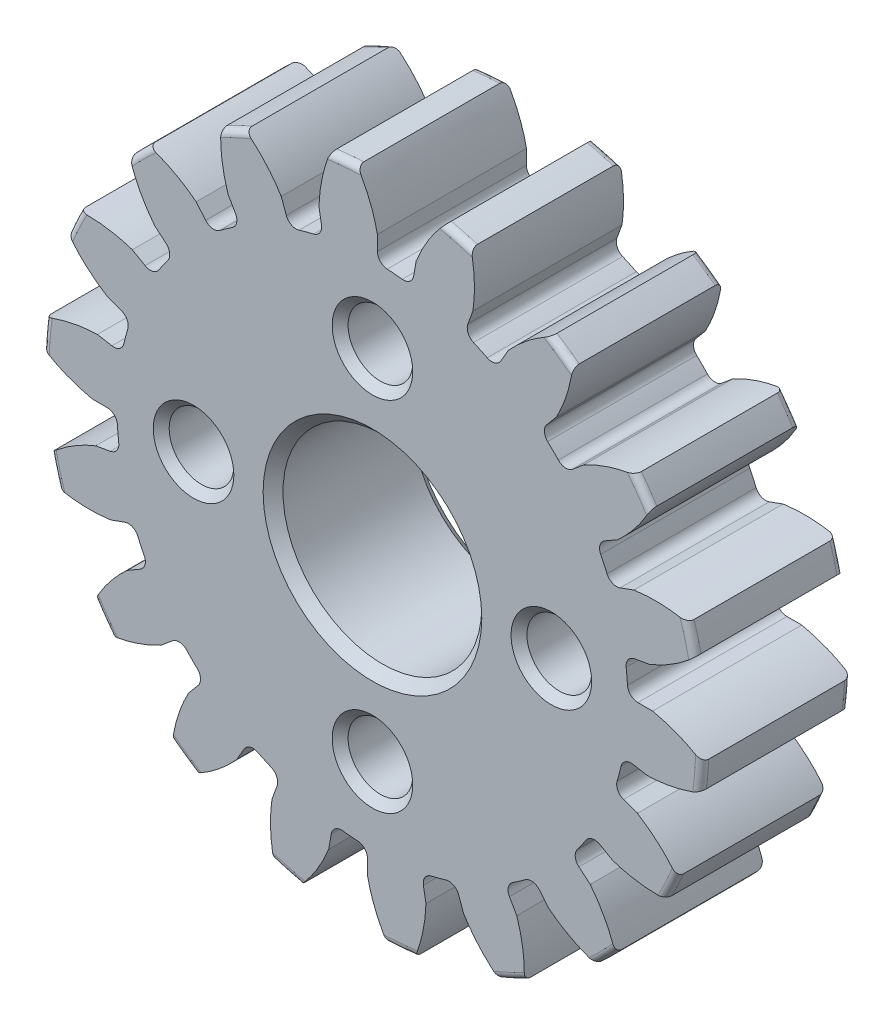
SolidWorks part; units mm, degrees
material "Plain Carbon Steel"
ref_plane "Front" through (0, 0, 0) normal (0, 0, 1) x (1, 0, 0)
ref_plane "Top" through (0, 0, 0) normal (0, 1, 0) x (1, 0, 0)
ref_plane "Right" through (0, 0, 0) normal (1, 0, 0) x (0, 0, -1)
sketch "Sketch1" plane through (0, 0, 0) normal (0, 0, 1) x (1, 0, 0)
  line L0 (-228.6, 0) -> (228.6, 0) construction
  circle A0 centre (0, 0) radius 10.541
  circle A1 centre (0, 0) radius 9.525 construction
  circle A3 centre (0, 0) radius 8.1598 construction
  dimension "D3" = 1.016
  dimension "D1" = 2.3813
extrude "Boss-Extrude1" add sketch "Sketch1" against normal blind 4.7625
sketch "Sketch2" plane through (0, 0, 0) normal (1, 0, 0) x (0, 0, -1)
  line L0 (4.7625, 0) -> (11.0998, 0)
  line L1 (4.7625, 0) -> (4.7625, 6.35)
  line L2 (4.7625, 6.35) -> (11.0998, 6.35)
  line L3 (11.0998, 6.35) -> (11.0998, 0)
  point P5 (11.0998, -6.35)
  point P6 (0, -10.541)
  point P7 (4.7625, -10.541)
  point P9 (0, 10.541)
revolve "Revolve1" add sketch "Sketch2" angle 360 mid plane about L0
fillet "Fillet2" radius 0.2108 3 edges at (10.541, 0, -4.7625) (10.541, 0, 0) (6.35, 0, -4.7625)
sketch "Sketch3" plane through (0, 0, 0) normal (0, 0, 1) x (1, 0, 0)
  line L0 (0, 0) -> (0, 10.541) construction
  line L1 (-3.0613, 8.4108) -> (0, 9.525)
  line L2 (-9.5921, 9.525) -> (9.5921, 9.525) construction
  line L3 (-9.0136, 6.2443) -> (9.0136, 12.8057) construction
  line L4 (-3.0613, 8.4108) -> (0, 0) construction
  line L5 (-7.3721, 5.0759) -> (0, 0) construction
  line L6 (-7.3721, 5.0759) -> (-2.3984, 12.2997) construction
  line L7 (-2.1265, 8.6943) -> (0, 0) construction
  line L8 (-2.1265, 8.6943) -> (0.0886, 9.2361) construction
  arc A0 (-3.0613, 8.4108) -> (-7.3721, 5.0759) centre (0, 0) ccw
  circle A1 centre (0, 0) radius 9.525 construction
  circle A2 centre (0, 0) radius 8.9506 construction
  arc A3 (-3.0613, 8.4108) -> (-2.1265, 8.6943) centre (0, 0) cw
  circle A4 centre (0, 0) radius 10.541 construction
  point P6 (0, 9.525)
  dimension "D1" = 3.2577
  dimension "Pressure Angle" = 20
  dimension "D2" = 5.5382
  dimension "D3" = 8.7705
  dimension "D4" = 0.9773
  dimension "D5" = 2.2804
sketch "Sketch4" plane through (0, 0, 0) normal (0, 0, 1) x (1, 0, 0)
  line L0 (0, 0) -> (0.827, 9.4526) construction
  line L1 (0.1576, 8.9492) -> (0.1576, 8.1582)
  line L2 (0, 9.525) -> (1.654, 9.3803) construction
  line L3 (1.3988, 8.8406) -> (1.2615, 8.0616)
  line L4 (0.1576, 8.1582) -> (0, 0) construction
  line L5 (0, 0) -> (0, 10.541) construction
  line L6 (-7.3721, 5.0759) -> (-2.3984, 12.2997) construction
  line L7 (-7.3721, 5.0759) -> (-2.3984, 12.2997) construction
  arc A0 (1.2615, 8.0616) -> (0.1576, 8.1582) centre (0, 0) ccw
  arc A1 (0, 9.525) -> (1.654, 9.3803) centre (0, 0) cw construction
  circle A2 centre (0, 0) radius 9.525 construction
  circle A3 centre (0, 0) radius 8.9506 construction
  circle A4 centre (0, 0) radius 8.1598 construction
  arc A5 (4.4978, 11.6964) -> (-2.3984, 12.2997) centre (0, 0) ccw
  spline S0 degree 2 poles (-2.3984, 12.2997) (-0.2792, 11.04) (0.1576, 8.9492) knots 0 0 0 1 1 1
  spline S1 degree 2 poles (4.4978, 11.6964) (2.1921, 10.8237) (1.3988, 8.8406) knots 0 0 0 1 1 1
  dimension "D1" = 1.6624
extrude "Cut-Extrude1" cut sketch "Sketch4" against normal through all
fillet "Fillet1" radius 0.3325 2 edges at (1.2615, 8.0616, -2.3813) (0.1576, 8.1582, -2.3813)
pattern_circular "CirPattern1" count 18 over 360 about axis through (0, 0, -4.7625) along (0, 0, 1) of "Cut-Extrude1", "Fillet1"
sketch "Sketch5" plane through (0, 0, 0) normal (0, 0, 1) x (1, 0, 0)
  line L0 (0, 4.3663) -> (0, 0) construction
  line L1 (-1.1906, 2.9433) -> (1.1906, 2.9433) construction
  line L2 (-1.1906, 2.9433) -> (-1.1906, 4.3663) construction
  line L3 (-1.1906, 4.3663) -> (1.1906, 4.3663) construction
  line L4 (1.1906, 2.9433) -> (1.1906, 4.3663) construction
  line L5 (-1.1906, 2.9433) -> (1.1906, 4.3663) construction
  line L6 (-1.1906, 4.3663) -> (1.1906, 2.9433) construction
  circle A0 centre (0, 0) radius 3.175
  point P3 (0, 3.6548)
  point P8 (0, 3.175)
  point P9 (0, -3.175)
  dimension "Bore Min" = 6.35
  dimension "Keyway Wd" = 2.3813
  dimension "Keyway Dpt." = 1.1913
extrude "Cut-Extrude2" cut sketch "Sketch5" against normal through all
sketch "Pitch Dia" plane through (0, 0, 0) normal (0, 0, 1) x (1, 0, 0)
  circle A0 centre (0, 0) radius 9.525 construction
  circle A1 centre (0, 0) radius 9.525 construction
sketch "Sketch6" plane through (0, 0, -4.7625) normal (0, 0, -1) x (-1, 0, 0)
  circle A0 centre (0, 0) radius 9.525
  dimension "D1" = 19.05
extrude "Cut-Extrude3" cut sketch "Sketch6" along normal through all
chamfer "Chamfer1" distance 0.3175 angle 45 2 edges at (3.175, 0, 0) (-3.175, 0, -4.7625)
sketch "Sketch7" plane through (0, 0, -4.7625) normal (0, 0, -1) x (-1, 0, 0)
  line L0 (0, 10.28) -> (0, -11.7668) construction
  line L1 (-13.3938, 0) -> (13.601, 0) construction
  circle A4 centre (0, 0) radius 5.715 construction
  circle A5 centre (0, 5.715) radius 1.0325
  circle A6 centre (-5.715, 0) radius 1.0325
  circle A7 centre (0, -5.715) radius 1.0325
  circle A8 centre (5.715, 0) radius 1.0325
  point P0 (0, 5.715)
  point P1 (5.715, 0)
  point P2 (0, -5.715)
  point P3 (-5.715, 0)
  dimension "D1" = 11.43
  dimension "D2" = 2.065
extrude "Cut-Extrude5" cut sketch "Sketch7" against normal through all both and the other way through all
chamfer "Chamfer2" distance 0.254 angle 45 8 edges at (1.0325, -5.715, -4.7625) (1.0325, -5.715, 0) (6.7475, 0, 0) (6.7475, 0, -4.7625) (-4.6825, 0, -4.7625) (-4.6825, 0, 0) (1.0325, 5.715, -4.7625) (1.0325, 5.715, 0)
equation "\"D1@Boss-Extrude1\" = \"Face Wd@Sketch2\""
equation "\"D1@Sketch4\" = 1.5708/(\"Number of Teeth@Sketch1\"/\"Ptich Dia@Sketch1\")"
equation "\"D1@Chamfer1\" = \"B Hub Dia@Sketch2\"*.025"
equation "\"D1@CirPattern1\" = \"Number of Teeth@Sketch1\""
equation "\"D1@Fillet1\" = \"D1@Sketch4\"*.2"
equation "\"D1@Fillet2\" = \"OD@Sketch1\"*.01"
equation "\"D1@Sketch1\" = 2.250/(\"Number of Teeth@Sketch1\"/\"Ptich Dia@Sketch1\")"
